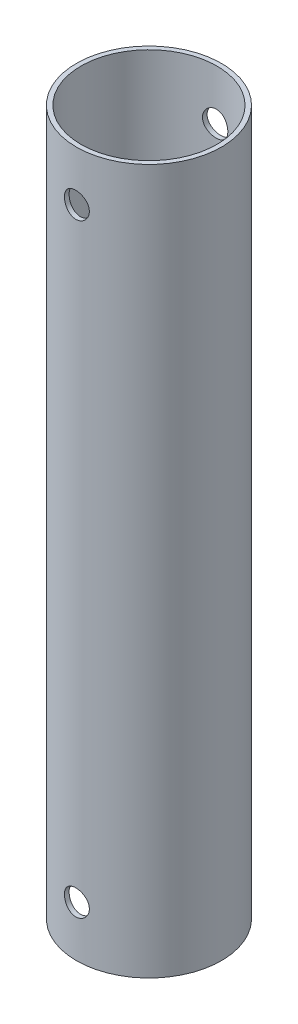
SolidWorks part; units mm, degrees
ref_plane "Front Plane" through (0, 0, 0) normal (0, 0, 1) x (1, 0, 0)
ref_plane "Top Plane" through (0, 0, 0) normal (0, 1, 0) x (1, 0, 0)
ref_plane "Right Plane" through (0, 0, 0) normal (1, 0, 0) x (0, 0, -1)
sketch "Sketch1" plane through (0, 0, 0) normal (0, 1, 0) x (1, 0, 0)
  circle A0 centre (0, 0) radius 15.875
  circle A1 centre (0, 0) radius 14.875
extrude "Boss-Extrude1" add sketch "Sketch1" along normal blind 154.2
sketch "Sketch2" plane through (0, 0, 0) normal (0, 0, 1) x (1, 0, 0)
  line L0 (-41.6535, 143.2) -> (41.3866, 143.2) construction
  line L1 (-41.6535, 11) -> (41.3866, 11) construction
  line L4 (0, 162.6204) -> (0, -4.7636) construction
  line L5 (0, 0) -> (-46.9074, 0) construction
  line L6 (-15.875, 154.2) -> (47.514, 154.2) construction
  circle A0 centre (-0.1335, 143.2) radius 2.75
  circle A1 centre (-0.1335, 11) radius 2.75
  dimension "D1" = 11
  dimension "D2" = 11
extrude "Cut-Extrude1" cut sketch "Sketch2" against normal blind 154.2 and the other way blind 154.2
